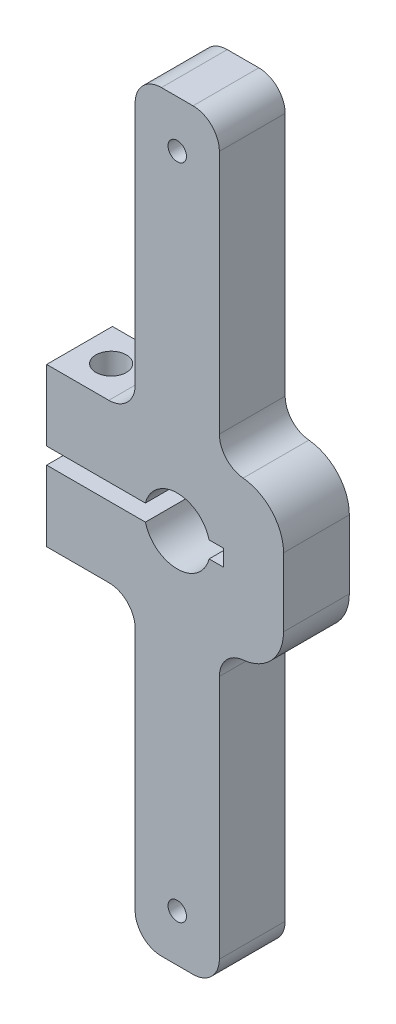
SolidWorks part; units mm, degrees
material "6061-T6 (SS)"
ref_plane "Front Plane" through (0, 0, 0) normal (0, 0, 1) x (1, 0, 0)
ref_plane "Top Plane" through (0, 0, 0) normal (0, 1, 0) x (1, 0, 0)
ref_plane "Right Plane" through (0, 0, 0) normal (1, 0, 0) x (0, 0, -1)
sketch "Sketch1" plane through (0, 0, 0) normal (0, 0, 1) x (1, 0, 0)
  line L0 (-21.4925, 7.62) -> (-6.2525, 7.62)
  line L1 (-21.4925, -7.62) -> (-21.4925, 7.62)
  line L2 (1.3675, 7.62) -> (1.3675, 0)
  line L3 (-6.2525, 7.62) -> (1.3675, 7.62)
  line L4 (55, 0) -> (-55, 0) construction
  line L5 (1.3675, 0) -> (1.3675, -7.62)
  line L6 (-6.2525, 7.62) -> (-6.2525, -7.62) construction
  line L7 (-21.4925, -7.62) -> (-6.2525, -7.62)
  line L8 (-6.2525, -7.62) -> (1.3675, -7.62)
  point P1 (0, 0)
extrude "Extrude1" add sketch "Sketch1" along normal blind 6.35
sketch "Sketch2" plane through (0, 0, 6.35) normal (0, 0, 1) x (1, 0, 0)
  line L0 (-21.4925, 0) -> (-4.445, 0) construction
  line L1 (-21.4925, 7.62) -> (-21.4925, -7.62) construction
  line L2 (-4.445, -0.7937) -> (-21.4925, -0.7938)
  line L3 (-4.445, -0.7937) -> (-4.445, 0.7938)
  line L4 (-21.4925, -0.7938) -> (-21.4925, 0.7938)
  line L5 (-4.445, 0.7938) -> (-21.4925, 0.7938)
  line L6 (-4.445, -0.7937) -> (-21.4925, 0.7938) construction
  line L7 (-21.4925, -0.7938) -> (-4.445, 0.7938) construction
  point P6 (-12.9687, 0)
extrude "Extrude2" cut sketch "Sketch2" against normal through all
sketch "Sketch4" plane through (0, 0, 6.35) normal (0, 0, 1) x (1, 0, 0)
  line L0 (-21.4925, 0.7938) -> (-21.4925, -0.7938) construction
  line L1 (-21.4925, 0) -> (-8.89, 0) construction
  circle A0 centre (-8.89, 0) radius 3.175
extrude "Extrude4" cut sketch "Sketch4" against normal through all
sketch "Sketch28" plane through (0, 0, 0) normal (0, 0, -1) x (-1, 0, 0)
  circle A0 centre (8.89, 0) radius 4.085
sketch "Sketch33" plane through (0, -7.62, 0) normal (0, -1, 0) x (1, 0, 0)
  line L0 (-21.4925, 3.175) -> (-18.4445, 3.175) construction
  line L1 (-21.4925, 6.35) -> (-21.4925, 0) construction
fillet "Fillet2" radius 4.318 2 edges at (1.3675, -7.62, 3.175) (1.3675, 7.62, 3.175)
hole_wizard "#32 (0.116) Diameter Hole1" positions "3DSketch5" profile "Sketch19" hole size "#32" standard "Ansi Inch" end condition through all
sketch3d "3DSketch5"
  point P3 (-18.4445, -7.62, 3.175)
sketch "Sketch19" plane through (-18.4445, -7.62, 3.175) normal (1, 0, 0) x (0, 0, -1)
  line L0 (0, 0) -> (0, 15.24)
  line L1 (0, 15.24) -> (1.4732, 15.24)
  line L2 (1.4732, 15.24) -> (1.4732, 0)
  line L5 (1.4732, 0) -> (0, 0)
  line L11 (0, -6.35) -> (0, 107.95) construction
  dimension "Thru Hole Dia." = 2.9464
  dimension "Thru Hole Depth" = 15.24
sketch "Sketch21" plane through (0, 7.62, 0) normal (0, 1, 0) x (1, 0, 0)
  line L0 (-8.89, 0) -> (-8.89, -6.35) construction
  line L4 (-8.89, 0) -> (-8.89, -6.35) construction
  line L5 (-2.9505, 0) -> (-21.4925, 0) construction
  line L6 (-8.89, 0) -> (-4.826, 0)
  line L7 (-4.826, 0) -> (-4.826, -6.35)
  line L8 (-4.826, -6.35) -> (-12.954, -6.35)
  line L9 (-12.954, -6.35) -> (-12.954, 0)
  line L10 (-12.954, 0) -> (-8.89, 0)
extrude "Extrude8" add sketch "Sketch21" along normal blind 28.6766
sketch "Sketch26" plane through (0, 0, 0) normal (0, 0, -1) x (-1, 0, 0)
  line L0 (8.89, 0) -> (8.89, 31.75) construction
hole_wizard "#50 (0.07) Diameter Hole1" positions "3DSketch7" profile "Sketch27" hole size "#50" standard "Ansi Inch"
sketch3d "3DSketch7"
  point P0 (-8.89, 31.75, 0)
sketch "Sketch27" plane through (-8.89, 31.75, 0) normal (1, 0, 0) x (0, 1, 0)
  line L0 (0, 0) -> (0, 6.8842)
  line L1 (0, 6.8842) -> (0.889, 6.35)
  line L2 (0.889, 6.35) -> (0.889, 0)
  line L5 (0.889, 0) -> (0, 0)
  line L10 (0, 6.8842) -> (-0.889, 6.35) construction
  line L11 (0, -6.35) -> (0, 107.95) construction
  dimension "Hole Dia." = 1.778
  dimension "Hole Depth" = 6.35
  dimension "Drill Angle" = 118
mirror "Mirror2" about plane through (0, 0, 0) normal (0, 1, 0) of "#50 (0.07) Diameter Hole1", "Extrude8"
fillet "Fillet1" radius 2.54 8 edges at (-12.954, 7.62, 3.175) (-4.826, 7.62, 3.175) (-12.954, 36.2966, 3.175) (-4.826, 36.2966, 3.175) (-12.954, -36.2966, 3.175) (-12.954, -7.62, 3.175) (-4.826, -7.62, 3.175) (-4.826, -36.2966, 3.175)
ref_plane "Plane1" through (0, 0, 10.16) normal (0, 0, 1) x (1, 0, 0)
sketch "Sketch34" plane through (0, 0, 10.16) normal (0, 0, 1) x (1, 0, 0)
  line L0 (1.3675, 0) -> (1.3675, -38.1) construction
  line L1 (1.3675, -3.302) -> (1.3675, 3.302) construction
